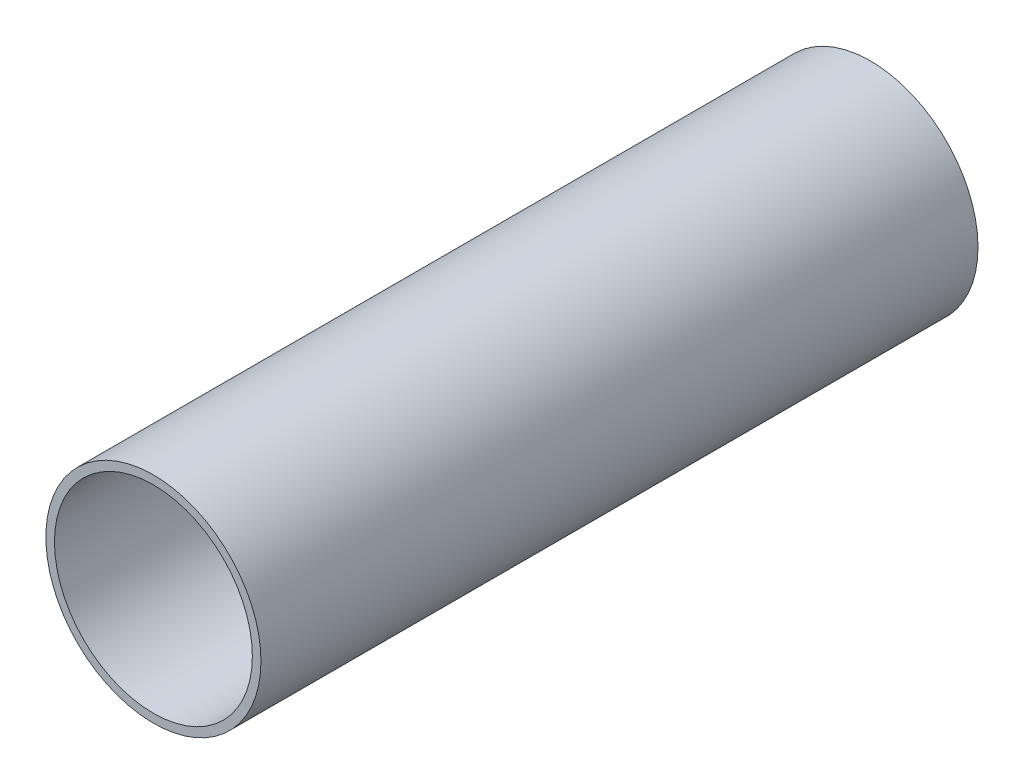
SolidWorks part; units mm, degrees
ref_plane "Ebene vorne" through (0, 0, 0) normal (0, 0, 1) x (1, 0, 0)
ref_plane "Ebene oben" through (0, 0, 0) normal (0, 1, 0) x (1, 0, 0)
ref_plane "Ebene rechts" through (0, 0, 0) normal (1, 0, 0) x (0, 0, -1)
sketch "Skizze1" plane through (0, 0, 0) normal (0, 0, 1) x (1, 0, 0)
  circle A0 centre (0, 0) radius 37.5
  dimension "D1" = 75
extrude "Linear-Austragen-Dünn1" add sketch "Skizze1" along normal blind 250 thin thin type one direction reverse wall 3
